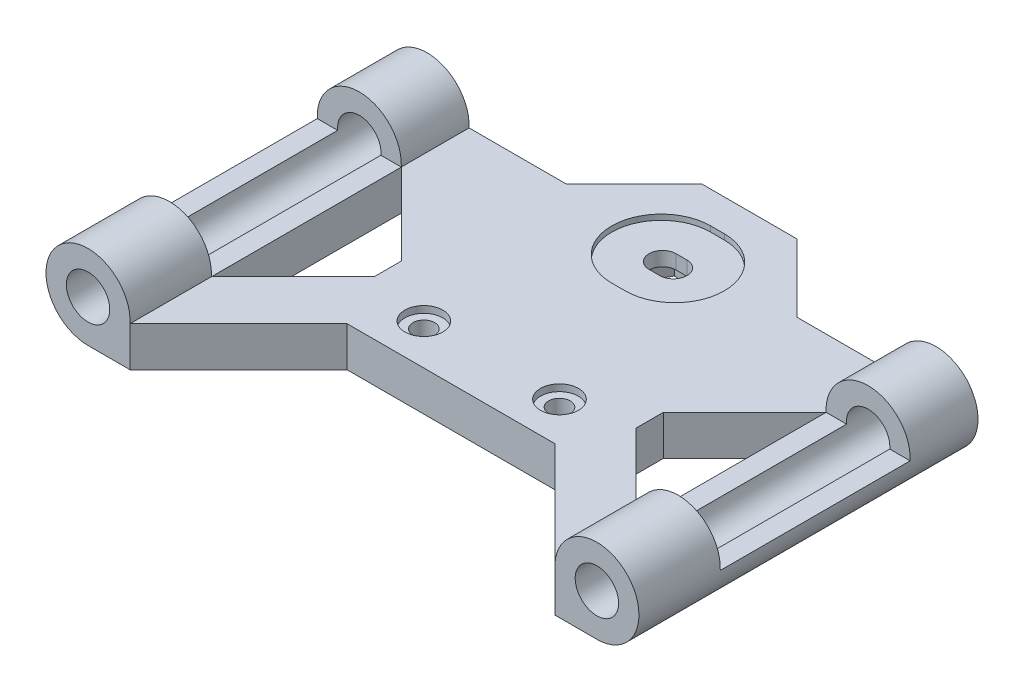
SolidWorks part; units mm, degrees
ref_plane "前视基准面" through (0, 0, 0) normal (0, 0, 1) x (1, 0, 0)
ref_plane "上视基准面" through (0, 0, 0) normal (0, 1, 0) x (1, 0, 0)
ref_plane "右视基准面" through (0, 0, 0) normal (1, 0, 0) x (0, 0, -1)
other "Configuration Table"
sketch "草图1" plane through (0, 0, 0) normal (0, 0, 1) x (1, 0, 0)
  line L0 (-46.5078, 2.4292) -> (-8.9878, 2.4292)
  line L1 (-43.4117, 5.3742) -> (-12.0839, 5.3742)
  line L3 (-37.4778, 5.3742) -> (-18.0178, 5.3742) construction
  circle A0 centre (-46.5078, 5.5292) radius 1.6
  circle A1 centre (-8.9878, 5.5292) radius 1.6
  circle A2 centre (-46.5078, 5.5292) radius 3.1
  circle A3 centre (-8.9878, 5.5292) radius 3.1
  circle A5 centre (-8.9878, 5.5292) radius 1.525 construction
  circle A6 centre (-46.5078, 5.5292) radius 1.525 construction
  dimension "D1" = 3.2
  dimension "D2" = 1.5
extrude "凸台-拉伸1" add sketch "草图1" along normal blind 25 contours A2 A0 | A3 L1 A2 L0 | A3 A1 region at (-27.7478, 3.8683, 0) region at (-48.6378, 7.6592, 0) region at (-11.0639, 3.3466, 0)
sketch "草图2" plane through (0, 5.3742, 0) normal (0, 1, 0) x (1, 0, 0)
  line L0 (-19.2478, 0) -> (-24.2478, 5)
  line L1 (-43.4117, 0) -> (-12.0839, 0) construction
  line L2 (-24.2478, 5) -> (-31.2478, 5)
  line L4 (-31.2478, 5) -> (-36.2478, 0)
  line L6 (-27.7478, 17.7449) -> (-27.7478, -46.0927) construction
  line L9 (-43.4078, -25) -> (-43.4078, 0) construction
  line L10 (-12.0878, 0) -> (-12.0878, -25) construction
  line L11 (-36.2478, 0) -> (-19.2478, 0)
  dimension "D1" = 5
  dimension "D2" = 7
  dimension "D3" = 45
extrude "凸台-拉伸2" add sketch "草图2" against normal up to surface (2.945 mm away) up to face at (-27.7478, 2.4292, 12.5)
sketch "草图3" plane through (0, 5.3742, 0) normal (0, 1, 0) x (1, 0, 0)
  line L0 (-28.1478, -1) -> (-27.3478, -1) construction
  line L1 (-28.1478, 0) -> (-27.3478, 0)
  line L2 (-28.1478, -2) -> (-27.3478, -2)
  line L3 (-24.2478, 5) -> (-31.2478, 5) construction
  arc A0 (-28.1478, 0) -> (-28.1478, -2) centre (-28.1478, -1) ccw
  arc A1 (-27.3478, -2) -> (-27.3478, 0) centre (-27.3478, -1) ccw
  point P2 (-27.7478, -1)
  point P10 (-27.7478, 5)
  dimension "D1" = 1
  dimension "D2" = 0.8
  dimension "15" = 6
extrude "切除-拉伸1" cut sketch "草图3" against normal through all
sketch "草图5" plane through (0, 2.4292, 0) normal (0, -1, 0) x (-1, 0, 0)
  line L17 (29.7149, -1) -> (28.5313, 1.05)
  line L18 (28.5313, 1.05) -> (26.1642, 1.05)
  line L19 (26.1642, 1.05) -> (24.9806, -1)
  line L20 (24.9806, -1) -> (26.1642, -3.05)
  line L21 (26.1642, -3.05) -> (28.5313, -3.05)
  line L22 (28.5313, -3.05) -> (29.7149, -1)
  line L23 (30.5149, -1) -> (29.3313, 1.05)
  line L24 (29.3313, 1.05) -> (26.9642, 1.05)
  line L25 (26.9642, 1.05) -> (25.7806, -1)
  line L26 (25.7806, -1) -> (26.9642, -3.05)
  line L27 (26.9642, -3.05) -> (29.3313, -3.05)
  line L28 (29.3313, -3.05) -> (30.5149, -1)
  circle A4 centre (27.3478, -1) radius 2.05 construction
  arc A5 (27.3478, 0) -> (27.3478, -2) centre (27.3478, -1) ccw construction
  circle A6 centre (28.1478, -1) radius 2.05 construction
  arc A7 (28.1478, -2) -> (28.1478, 0) centre (28.1478, -1) ccw construction
  line M17 (27.3478, 0) -> (28.1478, 0)
  arc M18 (28.1478, 0) -> (28.1478, -2) centre (28.1478, -1) cw
  line M19 (28.1478, -2) -> (27.3478, -2)
  arc M20 (27.3478, -2) -> (27.3478, 0) centre (27.3478, -1) cw
  dimension "D1" = 4.1
extrude "切除-螺母孔" cut sketch "草图5" against normal blind 1.5 contours L26 L25 L18 L19 L20 L21 | L25 L26 L21 L22 L17 L18 M20 M17 M18 M19 | L27 L28 L23 L24 L17 L22 region at (-29.0739, 2.4292, 1.9966) region at (-29.1626, 2.4292, -0.0478) region at (-26.333, 2.4292, -0.0478)
sketch "草图6" plane through (0, 5.3742, 0) normal (0, 1, 0) x (1, 0, 0)
  line L1 (-27.7478, -17.7348) -> (-27.7478, -33.5164) construction
  line L2 (-43.4117, -25) -> (-12.0839, -25) construction
  circle A0 centre (-32.7478, -14) radius 0.8
  circle A1 centre (-22.7478, -14) radius 0.8
  arc A3 (-27.3478, -2) -> (-27.3478, 0) centre (-27.3478, -1) ccw construction
  point P6 (-27.7478, -25)
  dimension "D2" = 1.6
  dimension "D3" = 13
  dimension "D1" = 10
extrude "切除-拉伸5" cut sketch "草图6" against normal through all
sketch "草图7" plane through (0, 5.3742, 0) normal (0, 1, 0) x (1, 0, 0)
  line L0 (-35.4078, -17) -> (-20.0839, -17)
  line L1 (-20.0839, -17) -> (-12.0839, -25)
  line L2 (-43.4078, -25) -> (-35.4078, -17)
  line L3 (-43.4117, -25) -> (-12.0839, -25) construction
  line L4 (-43.4078, -5) -> (-35.4078, -13)
  line L5 (-43.4078, -25) -> (-43.4078, 0) construction
  line L6 (-35.4078, -13) -> (-35.4078, -17)
  line L7 (-12.0878, -5) -> (-20.0839, -12.9961)
  line L8 (-12.0878, 0) -> (-12.0878, -25) construction
  line L9 (-20.0839, -12.9961) -> (-20.0839, -17)
  line L10 (-43.4078, -19) -> (-35.4078, -11)
  line L11 (-20.0839, -11.0039) -> (-12.0878, -19)
  line L12 (-27.7478, 9.0219) -> (-27.7478, -36.5602) construction
  line L13 (-24.2478, 5) -> (-31.2478, 5) construction
  line L14 (-43.4117, 0) -> (-36.2478, 0) construction
  line L15 (-43.4078, -5) -> (-43.4078, -19)
  line L16 (-12.0878, -5) -> (-12.0878, -19)
  line L17 (-37.4078, -11) -> (-37.4078, -13)
  line L18 (-18.0878, -11) -> (-18.0878, -13)
  circle A0 centre (-32.7478, -14) radius 0.8 construction
  point P26 (-27.7478, 5)
  line M18 (-43.4117, -25) -> (-12.0839, -25)
  dimension "D1" = 45
  dimension "D2" = 6
  dimension "D3" = 3
  dimension "D4" = 45
  dimension "D5" = 45
  dimension "D6" = 5
  dimension "D7" = 6
extrude "切除-拉伸6" cut sketch "草图7" against normal through all contours L4 L15 L10 L6 | L12 L0 L2 M18 | L0 L12 M18 | L16 L7 L9 L11 region at (-33.8065, 5.3742, 21.4574) region at (-21.6872, 5.3742, 21.4573) region at (-41.1578, 5.3742, 12) region at (-14.3378, 5.3742, 12)
sketch "草图9" plane through (-12.0878, 0, 0) normal (-1, 0, 0) x (0, 0, 1)
  line L0 (25, 3.9292) -> (25, 7.1292) construction
  line L1 (25, 3.9292) -> (25, 7.1292)
  line L2 (0, 8.6292) -> (0, 2.4292) construction
  line L3 (25, 3.9292) -> (0, 3.9292)
  line L4 (25, 3.9292) -> (25, 8.6292)
  line L5 (25, 8.6292) -> (0, 8.6292)
  line L6 (0, 3.9292) -> (0, 8.6292)
  line L7 (25, 8.6292) -> (0, 8.6292) construction
  line L8 (5, 5.3742) -> (19, 5.3742) construction
  line L9 (5, 5.3742) -> (19, 5.3742)
  line L12 (19, 5.3742) -> (5, 5.3742)
  line L13 (5, 5.3742) -> (5, 2.4292)
  line L14 (5, 2.4292) -> (19, 2.4292)
  line L15 (19, 2.4292) -> (19, 5.3742)
  line L17 (5, 8.6292) -> (5, 2.4292)
  line L18 (5, 2.4292) -> (19, 2.4292)
  line L19 (19, 2.4292) -> (19, 8.6292)
  line M5 (19, 5.3742) -> (5, 5.3742)
  dimension "D1" = 0
extrude "切除-拉伸9" cut sketch "草图9" against normal through all contours L19 L5 L17 M5 region at (-12.0878, 7.0017, 12)
ref_plane "基准面1" through (-27.7478, 0, 0) normal (1, 0, 0) x (0, 0, -1)
mirror "镜向1" about plane through (-27.7478, 0, 0) normal (1, 0, 0) of "切除-拉伸9"
sketch "草图10" plane through (0, 5.3742, 0) normal (0, 1, 0) x (1, 0, 0)
  circle A0 centre (-22.7478, -14) radius 1.4
  circle A1 centre (-32.7478, -14) radius 1.4
  circle A2 centre (-22.7478, -14) radius 0.8 construction
  circle A3 centre (-32.7478, -14) radius 0.8 construction
  dimension "D1" = 2.8
extrude "切除-拉伸11" cut sketch "草图10" against normal blind 0.5
sketch "草图11" plane through (0, 5.3742, 0) normal (0, 1, 0) x (1, 0, 0)
  line L0 (-27.2478, -1) -> (-28.2478, -1) construction
  line L1 (-27.2478, -4.65) -> (-28.2478, -4.65)
  line L2 (-27.2478, 2.65) -> (-28.2478, 2.65)
  arc A0 (-27.2478, -4.65) -> (-27.2478, 2.65) centre (-27.2478, -1) ccw
  arc A1 (-28.2478, 2.65) -> (-28.2478, -4.65) centre (-28.2478, -1) ccw
  circle A2 centre (-27.7478, -1) radius 3.65 construction
  point P2 (-27.7478, -1)
  dimension "D1" = 1
extrude "切除-拉伸12" cut sketch "草图11" against normal blind 0.4
